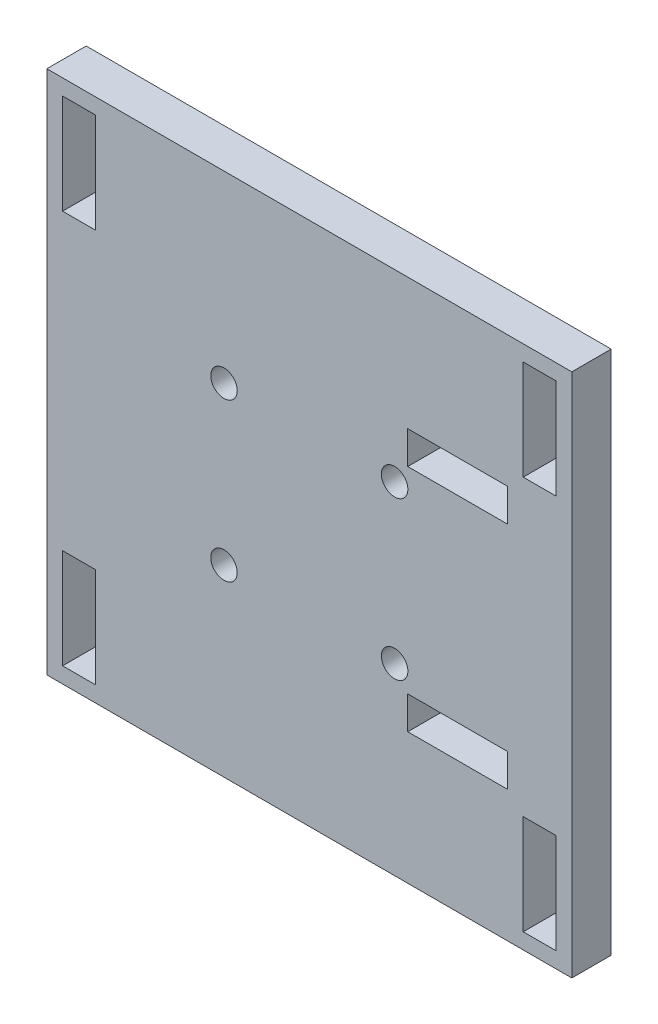
SolidWorks part; units mm, degrees
material "PET"
ref_plane "Alzado" through (0, 0, 0) normal (0, 0, 1) x (1, 0, 0)
ref_plane "Planta" through (0, 0, 0) normal (0, 1, 0) x (1, 0, 0)
ref_plane "Vista lateral" through (0, 0, 0) normal (1, 0, 0) x (0, 0, -1)
sketch "Sketch1" plane through (0, 0, 0) normal (0, 0, 1) x (1, 0, 0)
  line L0 (0, -1000) -> (0, 49000) construction
  line L5 (-1000, 0) -> (49000, 0) construction
  line L7 (-20, -20) -> (20, -20)
  line L8 (-20, -20) -> (-20, 20)
  line L9 (-20, 20) -> (20, 20)
  line L10 (20, -20) -> (20, 20)
  line L11 (-20, -20) -> (20, 20) construction
  line L12 (-20, 20) -> (20, -20) construction
  circle A0 centre (6.5, -6) radius 1.01
  circle A1 centre (-6.5, -6) radius 1.01
  circle A2 centre (6.5, 6) radius 1.01
  circle A3 centre (-6.5, 6) radius 1.01
  point P14 (0, 0)
  dimension "D3" = 2.02
  dimension "D1" = 6
  dimension "D2" = 6.5
  dimension "D4" = 40
  dimension "D5" = 40
extrude "Boss-Extrude1" add sketch "Sketch1" along normal blind 3
sketch "Sketch2" plane through (0, 0, 3) normal (0, 0, 1) x (1, 0, 0)
  line L0 (0, 20) -> (0, -20) construction
  line L1 (20, 20) -> (-20, 20) construction
  line L2 (-20, -20) -> (20, -20) construction
  line L3 (-20, 0) -> (20, 0) construction
  line L4 (-20, 20) -> (-20, -20) construction
  line L5 (20, -20) -> (20, 20) construction
  line L6 (18.8, 11.2) -> (16.3, 11.2)
  line L7 (-18.8, 18.8) -> (-16.3, 18.8)
  line L8 (-18.8, 18.8) -> (-18.8, 11.2)
  line L9 (-18.8, 11.2) -> (-16.3, 11.2)
  line L10 (-16.3, 18.8) -> (-16.3, 11.2)
  line L23 (7.5, 10) -> (15.1, 10)
  line L24 (7.5, 10) -> (7.5, 7.5)
  line L25 (7.5, 7.5) -> (15.1, 7.5)
  line L26 (15.1, 10) -> (15.1, 7.5)
  line L31 (18.8, 18.8) -> (18.8, 11.2)
  line L32 (18.8, 18.8) -> (16.3, 18.8)
  line L33 (16.3, 18.8) -> (16.3, 11.2)
  line L34 (16.3, -18.8) -> (16.3, -11.2)
  line L35 (18.8, -18.8) -> (16.3, -18.8)
  line L36 (18.8, -18.8) -> (18.8, -11.2)
  line L37 (18.8, -11.2) -> (16.3, -11.2)
  line L38 (-18.8, -11.2) -> (-16.3, -11.2)
  line L39 (-18.8, -18.8) -> (-18.8, -11.2)
  line L40 (-18.8, -18.8) -> (-16.3, -18.8)
  line L41 (-16.3, -18.8) -> (-16.3, -11.2)
  line L42 (15.1, -10) -> (15.1, -7.5)
  line L43 (7.5, -7.5) -> (15.1, -7.5)
  line L44 (7.5, -10) -> (7.5, -7.5)
  line L45 (7.5, -10) -> (15.1, -10)
  point P36 (15.1, 8.75)
  dimension "D1" = 7.6
  dimension "D2" = 2.5
  dimension "D3" = 1.2
  dimension "D4" = 1.2
  dimension "D5" = 2.5
  dimension "D6" = 7.6
  dimension "D7" = 1.2
  dimension "D8" = 1.2
extrude "Cut-Extrude1" cut sketch "Sketch2" against normal through all
